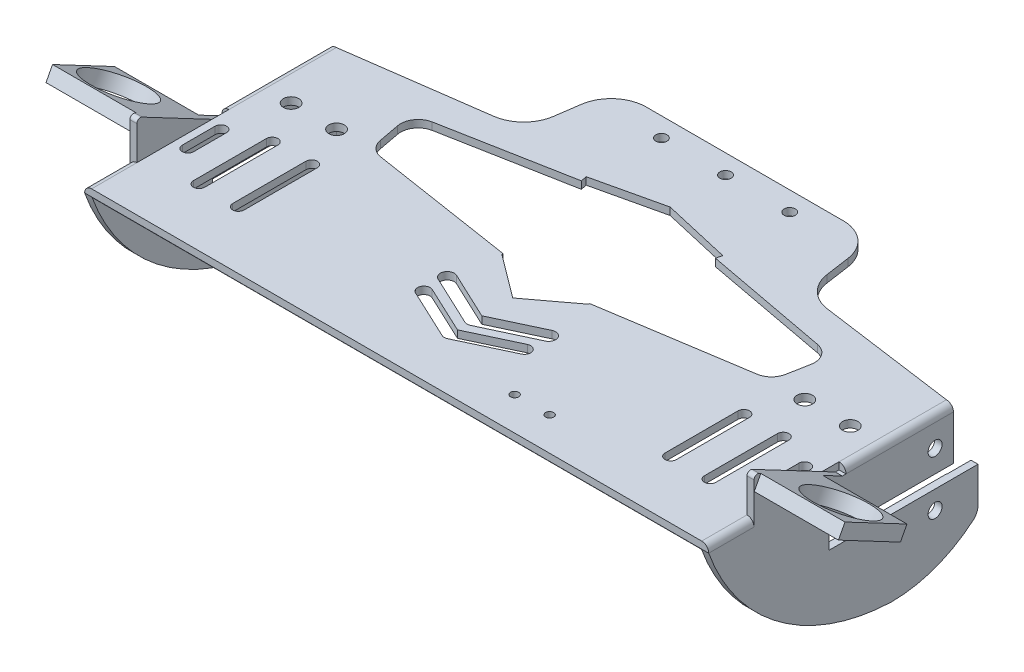
SolidWorks part; units mm, degrees
ref_plane "前视基准面" through (0, 0, 0) normal (0, 0, 1) x (1, 0, 0)
ref_plane "上视基准面" through (0, 0, 0) normal (0, 1, 0) x (1, 0, 0)
ref_plane "右视基准面" through (0, 0, 0) normal (1, 0, 0) x (0, 0, -1)
sketch "草图1" plane through (0, 0, 0) normal (0, 1, 0) x (1, 0, 0)
  line L1 (-89, 49.65) -> (89, 49.65)
  line L2 (-89, 49.65) -> (-89, -49.65)
  line L3 (-89, -49.65) -> (89, -49.65)
  line L4 (89, 49.65) -> (89, -49.65)
  line L5 (-89, 49.65) -> (89, -49.65) construction
  line L6 (-89, -49.65) -> (89, 49.65) construction
  point P0 (0, 0)
  dimension "D1" = 99.3
  dimension "D2" = 178
extrude "凸台-拉伸1" add sketch "草图1" along normal blind 40.1
sketch "草图2" plane through (0, 0, 49.65) normal (0, 0, 1) x (1, 0, 0)
  line L0 (-89, 0) -> (89, 0) construction
  line L1 (-86.9, 0) -> (86.9, 0)
  line L2 (-86.9, 0) -> (-86.9, 38)
  line L3 (-86.9, 38) -> (86.9, 38)
  line L4 (86.9, 0) -> (86.9, 38)
  line L5 (-89, 40.1) -> (89, 40.1) construction
  line L6 (-89, 40.1) -> (-89, 0) construction
  line L7 (89, 40.1) -> (89, 0) construction
  dimension "D1" = 2.1
  dimension "D2" = 2.1
  dimension "D3" = 2.1
extrude "切除-拉伸1" cut sketch "草图2" against normal through all
fillet "圆角2" radius 2 2 edges at (-89, 40.1, 0) (89, 40.1, 0)
sketch "草图4" plane through (0, 40.1, 0) normal (0, 1, 0) x (1, 0, 0)
  line L1 (-87, 49.65) -> (-87, -49.65) construction
  line L4 (87, -49.65) -> (87, 49.65) construction
  line L6 (87, 49.65) -> (-87, 49.65) construction
  line L11 (-36.8, 49.65) -> (-39.0309, 34.1016)
  line L12 (-47.5567, 25.6166) -> (-87, 20.15)
  line L13 (36.8, 49.65) -> (39.0309, 34.1016)
  line L14 (47.5567, 25.6166) -> (87, 20.15)
  line L15 (-36.8, 49.65) -> (-87, 49.65)
  line L16 (36.8, 49.65) -> (87, 49.65)
  line L18 (-87, 49.65) -> (-89, 49.65)
  line L19 (-89, 49.65) -> (-89, 35.5219)
  line L20 (-89, -49.65) -> (-89, 49.65) construction
  line L21 (-89, 35.5219) -> (-87, 35.5219)
  line L22 (-87, 35.5219) -> (-87, 20.15)
  line L23 (87, 49.65) -> (89, 49.65)
  line L24 (89, 49.65) -> (89, 35.5219)
  line L25 (89, 49.65) -> (89, -49.65) construction
  line L26 (89, 35.5219) -> (87, 35.5219)
  line L27 (87, 35.5219) -> (87, 20.15)
  arc A0 (47.5567, 25.6166) -> (39.0309, 34.1016) centre (48.9295, 35.5219) cw
  arc A1 (-47.5567, 25.6166) -> (-39.0309, 34.1016) centre (-48.9295, 35.5219) ccw
  point P6 (40.1, 26.65)
  point P22 (-40.1, 26.65)
  dimension "D1" = 10
  dimension "D3" = 73.6
  dimension "D4" = 80.2
extrude "切除-拉伸2" cut sketch "草图4" against normal through all
sketch "草图6" plane through (0, 40.1, 0) normal (0, 1, 0) x (1, 0, 0)
  line L0 (-36.8, 49.65) -> (-38.031, 41.0702)
  line L1 (-36.8, 49.65) -> (-28.1324, 49.65)
  line L2 (28.1324, 49.65) -> (36.8, 49.65)
  line L3 (36.8, 49.65) -> (38.031, 41.0702)
  arc A0 (38.031, 41.0702) -> (28.1324, 49.65) centre (28.1324, 39.65) ccw
  arc A1 (-28.1324, 49.65) -> (-38.031, 41.0702) centre (-28.1324, 39.65) ccw
  arc A6 (37.501, 43.1471) -> (38.031, 41.0702) centre (67.3147, 49.65) ccw
  dimension "D2" = 10
extrude "切除-拉伸3" cut sketch "草图6" against normal through all contours A0 L0 L1 | A1 L1 L2 region at (-35.1715, 40.1, -47.7712) region at (35.1715, 40.1, -47.7712)
sketch "草图8" plane through (0, 40.1, 0) normal (0, 1, 0) x (1, 0, 0)
  line L0 (0, 0) -> (0, 49.65) construction
  line L1 (28.1324, 49.65) -> (-28.1324, 49.65) construction
  line L2 (0, 28.35) -> (-19.5, 23.8654)
  line L3 (-19.5, 23.8654) -> (-12.3279, -7.3205)
  line L4 (-12.3279, -7.3205) -> (0, -16.55)
  line L5 (0, 0) -> (0, -49.65) construction
  line L6 (-87, -49.65) -> (87, -49.65) construction
  line L7 (12.3279, -7.3205) -> (0, -16.55)
  line L8 (19.5, 23.8654) -> (12.3279, -7.3205)
  line L9 (0, 28.35) -> (19.5, 23.8654)
  line L10 (0, -27.5506) -> (-14.4638, -20.751) construction
  line L11 (-0.8416, -29.3407) -> (-15.3054, -22.5412)
  line L12 (0, -25.3648) -> (-13.6222, -18.9609)
  line L13 (0, -34.2872) -> (-14.33, -27.5506) construction
  line L14 (-0.7615, -35.907) -> (-15.0915, -29.1704)
  line L15 (0, -32.3093) -> (-13.5685, -25.9307)
  line L16 (0, -27.5506) -> (14.4638, -20.751) construction
  line L17 (0.7598, -29.3407) -> (15.3054, -22.5412)
  line L18 (0, -25.3648) -> (13.6222, -18.9609)
  line L19 (0, -34.2872) -> (14.33, -27.5506) construction
  line L20 (0.7615, -35.907) -> (15.0915, -29.1704)
  line L21 (0, -32.3093) -> (13.5685, -25.9307)
  line L22 (22.519, 16.4386) -> (19.6042, 0.9065)
  line L23 (25.2872, -4.9563) -> (53.6458, -0.5436)
  line L24 (57.7913, 3.4748) -> (58.9414, 9.6035)
  line L25 (54.9494, 15.4399) -> (28.3555, 20.4306)
  line L26 (-57.7913, 3.4748) -> (-58.9414, 9.6035)
  line L27 (-25.2872, -4.9563) -> (-53.6458, -0.5436)
  line L28 (-22.519, 16.4386) -> (-19.6042, 0.9065)
  line L29 (-54.9494, 15.4399) -> (-28.3555, 20.4306)
  line L30 (-72.8787, -12.2804) -> (-72.8787, -33.1326) construction
  line L31 (-71.2555, -12.2804) -> (-71.2555, -33.1326)
  line L32 (-74.5019, -12.2804) -> (-74.5019, -33.1326)
  line L33 (-61.641, -12.2804) -> (-61.641, -33.1326) construction
  line L34 (-60.0178, -12.2804) -> (-60.0178, -33.1326)
  line L35 (-63.2642, -12.2804) -> (-63.2642, -33.1326)
  line L36 (-83.2424, -16.55) -> (-83.2424, -25.9307) construction
  line L37 (-81.6191, -16.55) -> (-81.6191, -25.9307)
  line L38 (-84.8656, -16.55) -> (-84.8656, -25.9307)
  line L39 (61.641, -12.2804) -> (61.641, -33.1326) construction
  line L40 (60.0178, -12.2804) -> (60.0178, -33.1326)
  line L41 (63.2642, -12.2804) -> (63.2642, -33.1326)
  line L42 (72.8787, -12.2804) -> (72.8787, -33.1326) construction
  line L43 (71.2555, -12.2804) -> (71.2555, -33.1326)
  line L44 (74.5019, -12.2804) -> (74.5019, -33.1326)
  line L45 (83.2424, -16.55) -> (83.2424, -25.9307) construction
  line L46 (81.6191, -16.55) -> (81.6191, -25.9307)
  line L47 (84.8656, -16.55) -> (84.8656, -25.9307)
  line L48 (-18.3, 49.65) -> (-18.3, 44.15) construction
  line L49 (-27.1278, 49.65) -> (-12.028, 49.65) construction
  line L50 (-18.3, 44.15) -> (0, 44.15) construction
  arc A4 (-13.6222, -18.9609) -> (-15.3054, -22.5412) centre (-14.4638, -20.751) ccw
  arc A6 (-13.5685, -25.9307) -> (-15.0915, -29.1704) centre (-14.33, -27.5506) ccw
  arc A8 (13.6222, -18.9609) -> (15.3054, -22.5412) centre (14.4638, -20.751) cw
  arc A10 (13.5685, -25.9307) -> (15.0915, -29.1704) centre (14.33, -27.5506) cw
  arc A11 (-0.7615, -35.907) -> (0.7615, -35.907) centre (0, -34.2872) ccw
  arc A12 (-0.8416, -29.3407) -> (0.7598, -29.3407) centre (-0.0409, -27.7399) ccw
  arc A13 (58.9414, 9.6035) -> (54.9494, 15.4399) centre (54.0272, 10.5257) ccw
  arc A14 (22.519, 16.4386) -> (28.3555, 20.4306) centre (27.4332, 15.5164) cw
  arc A15 (53.6458, -0.5436) -> (57.7913, 3.4748) centre (52.8771, 4.397) ccw
  arc A16 (19.6042, 0.9065) -> (25.2872, -4.9563) centre (24.5185, -0.0157) ccw
  arc A17 (-58.9414, 9.6035) -> (-54.9494, 15.4399) centre (-54.0272, 10.5257) cw
  arc A18 (-53.6458, -0.5436) -> (-57.7913, 3.4748) centre (-52.8771, 4.397) cw
  arc A19 (-19.6042, 0.9065) -> (-25.2872, -4.9563) centre (-24.5185, -0.0157) cw
  arc A20 (-22.519, 16.4386) -> (-28.3555, 20.4306) centre (-27.4332, 15.5164) ccw
  circle A23 centre (-66.7728, -0.0157) radius 2.2
  circle A24 centre (-79.7448, -0.0157) radius 2.2
  circle A25 centre (79.7448, -0.0157) radius 2.2
  circle A26 centre (66.7728, -0.0157) radius 2.2
  arc A27 (-71.2555, -12.2804) -> (-74.5019, -12.2804) centre (-72.8787, -12.2804) ccw
  arc A28 (-74.5019, -33.1326) -> (-71.2555, -33.1326) centre (-72.8787, -33.1326) ccw
  arc A29 (-60.0178, -12.2804) -> (-63.2642, -12.2804) centre (-61.641, -12.2804) ccw
  arc A30 (-63.2642, -33.1326) -> (-60.0178, -33.1326) centre (-61.641, -33.1326) ccw
  arc A31 (-81.6191, -16.55) -> (-84.8656, -16.55) centre (-83.2424, -16.55) ccw
  arc A32 (-84.8656, -25.9307) -> (-81.6191, -25.9307) centre (-83.2424, -25.9307) ccw
  arc A33 (60.0178, -12.2804) -> (63.2642, -12.2804) centre (61.641, -12.2804) cw
  arc A34 (63.2642, -33.1326) -> (60.0178, -33.1326) centre (61.641, -33.1326) cw
  arc A35 (71.2555, -12.2804) -> (74.5019, -12.2804) centre (72.8787, -12.2804) cw
  arc A36 (74.5019, -33.1326) -> (71.2555, -33.1326) centre (72.8787, -33.1326) cw
  arc A37 (81.6191, -16.55) -> (84.8656, -16.55) centre (83.2424, -16.55) cw
  arc A38 (84.8656, -25.9307) -> (81.6191, -25.9307) centre (83.2424, -25.9307) cw
  circle A42 centre (-18.3, 44.15) radius 1.6
  circle A43 centre (0, 44.15) radius 1.6
  circle A44 centre (18.3, 44.15) radius 1.6
  point P7 (0, 40.65)
  point P24 (-7.2319, -24.1508)
  point P29 (-7.165, -30.9189)
  point P42 (7.2319, -24.1508)
  point P49 (7.165, -30.9189)
  point P72 (-72.8787, -22.7065)
  point P89 (-61.641, -22.7065)
  point P96 (-83.2424, -21.2403)
  point P103 (61.641, -22.7065)
  point P110 (72.8787, -22.7065)
  point P117 (83.2424, -21.2403)
  dimension "D11" = 1.9781
  dimension "D12" = 1.7899
  dimension "D13" = 1.7899
  dimension "D14" = 5
  dimension "D15" = 5
  dimension "D16" = 4.4
  dimension "D17" = 4.4
  dimension "D7" = 44.9
  dimension "D8" = 39
  dimension "D9" = 32
  dimension "D10" = 15.4
extrude "切除-拉伸4" cut sketch "草图8" against normal through all
sketch "草图9" plane through (-89, 0, 0) normal (-1, 0, 0) x (0, 0, 1)
  line L4 (-3.9924, 34.7018) -> (22.4339, 34.7018)
  line L5 (22.3848, 35.6994) -> (37.5202, 37.1925)
  line L6 (37.5693, 37.1949) -> (-3.4557, 37.1949)
  line L7 (-3.9262, 36.8641) -> (-4.4629, 35.3709)
  arc A4 (37.5202, 37.1925) -> (37.5693, 37.1949) centre (37.5693, 36.6949) ccw
  arc A5 (-3.4557, 37.1949) -> (-3.9262, 36.8641) centre (-3.4557, 36.6949) ccw
  arc A6 (22.4339, 34.7018) -> (22.3848, 35.6994) centre (22.4339, 35.2018) ccw
  arc A7 (-3.9924, 34.7018) -> (-4.4629, 35.3709) centre (-3.9924, 35.2018) cw
  dimension "D1" = 0.5
sketch "草图11" plane through (-89, 0, 0) normal (-1, 0, 0) x (0, 0, 1)
  line L0 (-35.5219, 0) -> (49.65, 0) construction
  line L1 (-20.15, 0) -> (-20.15, 40.1) construction
  line L2 (-20.15, 31.5533) -> (-20.15, 40.1)
  line L3 (-35.5219, 0) -> (-35.5219, 38.1) construction
  line L4 (-20.15, 31.5533) -> (-35.5219, 31.5533)
  line L5 (-35.5219, 31.5533) -> (-35.5219, 25.3757)
  line L6 (-35.5219, 25.3757) -> (15.2781, 25.3757)
  line L7 (15.2781, 25.3757) -> (15.2781, 21.6757)
  line L8 (15.2781, 21.6757) -> (-35.5219, 21.6757)
  line L9 (49.65, 38.1) -> (49.65, 0) construction
  line L10 (-20.15, 40.1) -> (-35.5219, 40.1)
  line L11 (-35.5219, 40.1) -> (-35.5219, 31.5533)
  line L12 (-35.5219, 25.3757) -> (-35.5219, 21.6757)
  line L13 (-35.5219, 21.6757) -> (-35.5219, 0)
  line L14 (-35.5219, 0) -> (-8.2396, 0)
  line L15 (-6.3135, 0) -> (49.65, 0)
  line L16 (49.65, 0) -> (49.65, 38.1)
  arc A0 (49.65, 38.1) -> (-6.3135, 0) centre (-4.4168, 57.3652) cw
  arc A1 (-35.5219, 21.6757) -> (-8.2396, 0) centre (1.0945, 39.7558) ccw
  line M11 (49.65, 38.1) -> (-35.5219, 38.1)
  line M12 (-35.5219, 38.1) -> (-35.5219, 0)
  line M13 (-35.5219, 0) -> (49.65, 0)
  line M14 (49.65, 0) -> (49.65, 38.1)
  dimension "D1" = 50.8
  dimension "D2" = 34.3719
  dimension "D3" = 3.7
extrude "切除-拉伸6" cut sketch "草图11" against normal up to next contours L4 L2 M11 M12 | L10 L11 L2 M11 | A1 M12 M13 | A0 L15 M14 | L8 L7 L6 M12 region at (-89, 34.8267, -27.8359) region at (-89, 39.1, -27.8359) region at (-89, 10.263, 37.2191) region at (-89, 23.5257, -10.1219) region at (-89, 6.1552, -28.0302)
sketch "草图12" plane through (89, 0, 0) normal (1, 0, 0) x (0, 0, -1)
  line L9 (35.5219, 40.1) -> (35.5219, 31.5533) construction
  line L10 (20.15, 40.1) -> (35.5219, 40.1) construction
  line L11 (20.15, 31.5533) -> (20.15, 40.1) construction
  line L12 (20.15, 31.5533) -> (35.5219, 31.5533) construction
  line L14 (35.5219, 25.3757) -> (-15.3185, 25.3757)
  line L15 (-15.3185, 25.3757) -> (-15.3185, 21.6757)
  line L16 (-15.3185, 21.6757) -> (35.5219, 21.6757)
  line L17 (35.5219, 25.3757) -> (35.5219, 21.6757)
  line L22 (35.5219, 40.1) -> (35.5219, 31.5533)
  line L23 (20.15, 40.1) -> (35.5219, 40.1)
  line L24 (20.15, 31.5533) -> (20.15, 40.1)
  line L25 (20.15, 31.5533) -> (35.5219, 31.5533)
  dimension "D1" = 50.8404
extrude "切除-拉伸7" cut sketch "草图12" against normal up to next
sketch "草图13" plane through (89, 0, 0) normal (1, 0, 0) x (0, 0, -1)
  line L3 (2.5201, 0) -> (35.5219, 0) construction
  line L4 (35.5219, 21.6757) -> (35.5219, 0)
  line L5 (35.5219, 0) -> (2.5201, 0)
  arc A1 (2.5201, 0) -> (35.5219, 21.6757) centre (2.5201, 35.9609) ccw
  arc A2 (-49.65, 38.1) -> (2.5201, 0) centre (4.4168, 57.3652) ccw construction
extrude "切除-拉伸8" cut sketch "草图13" against normal through all
sketch "草图14" plane through (-89, 0, 0) normal (-1, 0, 0) x (0, 0, 1)
  line L1 (-20.15, 31.5533) -> (-35.5219, 31.5533)
  line L2 (-20.15, 31.5533) -> (-20.15, 25.3757)
  line L3 (-20.15, 25.3757) -> (-35.5219, 25.3757)
  line L4 (-35.5219, 31.5533) -> (-35.5219, 25.3757)
extrude "切除-拉伸9" cut sketch "草图14" against normal through all both and the other way through all
fillet "圆角5" radius 2 1 edges at (-88, 21.6757, -35.5219) type face fillet first side face at (-87.6333, 21.6757, -13.4669) second side face at (-87.6333, 9.124, -24.1133)
fillet "圆角6" radius 2 1 edges at (88, 21.6757, -35.5219) type face fillet first side face at (87.6333, 21.6757, -13.4534) second side face at (87.6333, 7.544, -20.2225)
sketch "草图15" plane through (89, 0, 0) normal (1, 0, 0) x (0, 0, -1)
  line L0 (-49.65, 38.1) -> (-15.0631, 38.1) construction
  line L1 (20.15, 38.1) -> (-49.65, 38.1) construction
  line L2 (7.3369, 38.1) -> (-37.4631, 38.1)
  line L3 (-37.4631, 38.1) -> (-37.4631, 27.6)
  line L4 (-37.4631, 27.6) -> (7.3369, 27.6)
  line L5 (7.3369, 27.6) -> (7.3369, 38.1)
  point P8 (-15.0631, 38.1)
extrude "凸台-拉伸2" add sketch "草图15" along normal blind 2
sketch "草图16" plane through (91, 0, 0) normal (1, 0, 0) x (0, 0, -1)
  line L0 (-37.4631, 38.1) -> (-21.8983, 38.1) construction
  line L1 (7.3369, 38.1) -> (-37.4631, 38.1) construction
  line L2 (-21.8983, 32.7435) -> (-21.8983, 54.1985) construction
  line L3 (-30.0183, 43.93) -> (-21.8983, 38.1) construction
  line L4 (-30.0183, 38.1) -> (-30.0183, 43.93) construction
  line L5 (-21.8983, 38.1) -> (-13.7752, 32.2678) construction
  line L6 (-30.6015, 43.1177) -> (-29.4351, 44.7423)
  line L7 (-30.6015, 43.1177) -> (-31.7823, 41.4732)
  line L8 (-31.7823, 41.4732) -> (-15.536, 29.8087)
  line L9 (-15.536, 29.8087) -> (-13.2032, 33.0579)
  line L10 (-29.4351, 44.7423) -> (-13.2032, 33.0579)
  point P10 (-21.8983, 38.1)
  point P14 (-30.0183, 43.93)
  dimension "D1" = 8.12
extrude "凸台-拉伸3" add sketch "草图16" along normal blind 20
sketch "草图17" plane through (0, 15.5146, -11.168) normal (0, 0.8116, -0.5842) x (1, 0, 0)
  line L0 (91, -50.0287) -> (111, -30.0287) construction
  line L1 (91, -30.0287) -> (111, -50.0287) construction
  circle A0 centre (101, -40.0287) radius 9
extrude "切除-拉伸10" cut sketch "草图17" against normal blind 5
sketch "草图18" plane through (89, 0, 0) normal (1, 0, 0) x (0, 0, -1)
  line L0 (-32.4893, 38.1) -> (-32.4893, 54.845) construction
  line L4 (-20.071, 38.1) -> (-20.071, 54.845)
  line L5 (-32.4893, 54.845) -> (-20.071, 54.845)
  line L6 (-32.4893, 38.1) -> (-20.071, 38.1)
  line L7 (-32.4893, 54.845) -> (-32.4893, 38.1)
extrude "切除-拉伸11" cut sketch "草图18" against normal blind 2
sketch "草图19" plane through (91, 0, 0) normal (-1, 0, 0) x (0, 0, 1)
  line L0 (20.2076, 38.1) -> (29.4351, 44.7423)
  line L1 (31.7823, 33.3445) -> (31.7823, 49.6018) construction
  line L3 (29.4351, 44.7423) -> (31.7823, 46.4319)
  line L4 (31.7823, 46.4319) -> (31.7823, 41.4732)
  line L5 (20.2076, 38.1) -> (34.2826, 38.1) construction
  line L6 (27.0842, 38.1) -> (37.4631, 38.1) construction
  line L7 (20.2076, 38.1) -> (31.7823, 38.1)
  line L8 (31.7823, 38.1) -> (31.7823, 41.4732)
  point P9 (31.7823, 41.4732)
extrude "凸台-拉伸4" add sketch "草图19" along normal blind 4
sketch "草图20" plane through (87, 0, 0) normal (-1, 0, 0) x (0, 0, 1)
  line L0 (22.986, 40.1) -> (31.7823, 40.1)
  line L1 (31.7823, 40.1) -> (31.7823, 46.4319)
  line L2 (31.7823, 46.4319) -> (22.986, 40.1)
extrude "凸台-拉伸5" add sketch "草图20" along normal blind 1.5
ref_plane "基准面1" through (0, 0, 0) normal (-1, 0, 0) x (0, 1, 0)
sketch "草图21" plane through (-89, 0, 0) normal (-1, 0, 0) x (0, 0, 1)
  line L0 (49.65, 38.1) -> (-20.15, 38.1) construction
  line L1 (19.0608, 38.1) -> (32.4979, 38.1)
  line L2 (19.0608, 38.1) -> (19.0608, 58.3811)
  line L3 (19.0608, 58.3811) -> (32.4979, 58.3811)
  line L4 (32.4979, 38.1) -> (32.4979, 58.3811)
extrude "切除-拉伸12" cut sketch "草图21" against normal blind 2
mirror "镜向2" about plane through (0, 0, 0) normal (-1, 0, 0) of "凸台-拉伸5", "凸台-拉伸2", "凸台-拉伸3", "切除-拉伸10", "凸台-拉伸4"
sketch "草图22" plane through (0, 40.1, 0) normal (0, 1, 0) x (1, 0, 0)
  line L0 (-38.9134, 18.4493) -> (-28.3555, 20.4306) construction
  line L2 (-28.3555, 20.4306) -> (-54.9494, 15.4399) construction
  line L3 (-28.3555, 20.4306) -> (0, 25.7518) construction
  line L4 (0, 110.453) -> (0, -110.453) construction
  line L5 (-28.3555, 20.4306) -> (-19.1091, 22.1658)
  line L6 (-19.5, 23.8654) -> (-12.3279, -7.3205) construction
  line L7 (-33.1335, -3.7354) -> (-25.2872, -4.9563) construction
  line L8 (-53.6458, -0.5436) -> (-25.2872, -4.9563) construction
  line L9 (-25.2872, -4.9563) -> (0, -8.891) construction
  line L10 (-19.1091, 22.1658) -> (-12.4108, -6.9599)
  line L11 (-12.4108, -6.9599) -> (-25.2872, -4.9563)
  line L12 (-22.519, 16.4386) -> (-19.6042, 0.9065)
  line L13 (28.3555, 20.4306) -> (19.1091, 22.1658)
  line L14 (19.1091, 22.1658) -> (12.4108, -6.9599)
  line L15 (12.4108, -6.9599) -> (25.2872, -4.9563)
  line L16 (22.519, 16.4386) -> (19.6042, 0.9065)
  arc A0 (-25.2872, -4.9563) -> (-19.6042, 0.9065) centre (-24.5185, -0.0157) ccw
  arc A1 (-28.3555, 20.4306) -> (-22.519, 16.4386) centre (-27.4332, 15.5164) cw
  arc A2 (28.3555, 20.4306) -> (22.519, 16.4386) centre (27.4332, 15.5164) ccw
  arc A3 (25.2872, -4.9563) -> (19.6042, 0.9065) centre (24.5185, -0.0157) cw
extrude "切除-拉伸13" cut sketch "草图22" against normal blind 6
ref_plane "基准面2" through (0, 30.6223, 42.6506) normal (0, 0.5832, 0.8123) x (1, 0, 0)
sketch "草图23" plane through (0, 30.6223, 42.6506) normal (0, 0.5832, 0.8123) x (1, 0, 0)
  line L1 (-96.792, 24.8771) -> (-78.9143, 24.8771)
  line L2 (-96.792, 24.8771) -> (-96.792, 16.5031)
  line L3 (-96.792, 16.5031) -> (-78.9143, 16.5031)
  line L4 (-78.9143, 24.8771) -> (-78.9143, 16.5031)
  line L5 (81.9311, 26.5695) -> (95.5678, 26.5695)
  line L6 (81.9311, 26.5695) -> (81.9311, 13.5683)
  line L7 (81.9311, 13.5683) -> (95.5678, 13.5683)
  line L8 (95.5678, 26.5695) -> (95.5678, 13.5683)
extrude "切除-拉伸14" cut sketch "草图23" along normal blind 4
fillet "圆角12" radius 0.5 2 edges at (-88.25, 46.2029, 31.4641) (-88.25, 45.7597, 31.7823)
sketch "草图25" plane through (0, 40.1, 0) normal (0, 1, 0) x (1, 0, 0)
  line L0 (29.1327, -49.65) -> (29.1327, -40.15) construction
  line L1 (-87, -49.65) -> (87, -49.65) construction
  line L2 (34.1327, -40.15) -> (24.1327, -40.15) construction
  circle A0 centre (24.1327, -40.15) radius 1.15
  circle A1 centre (34.1327, -40.15) radius 1.15
  point P7 (29.1327, -40.15)
extrude "切除-拉伸15" cut sketch "草图25" against normal blind 5
sketch "草图28" plane through (91, 0, 0) normal (1, 0, 0) x (0, 0, -1)
  line L0 (-31.7823, 38.1) -> (-37.4631, 38.1)
  line L1 (-37.4631, 38.1) -> (-37.4631, 27.6)
  line L2 (-37.4631, 27.6) -> (7.3369, 27.6)
  line L3 (7.3369, 27.6) -> (7.3369, 38.1)
  line L4 (7.3369, 38.1) -> (-12.0153, 38.1)
  line L5 (7.3369, 38.1) -> (-20.2076, 38.1) construction
  line L8 (-31.7823, 29.3719) -> (-31.7823, 38.1)
  line L9 (-13.2032, 33.0579) -> (-13.2032, 38.1)
  line L10 (-13.2032, 38.1) -> (-12.0153, 38.1)
  line L11 (-13.2032, 33.0579) -> (-13.2032, 29.3719)
  line L12 (-13.2032, 29.3719) -> (-31.7823, 29.3719)
extrude "切除-拉伸17" cut sketch "草图28" against normal blind 2
mirror "镜向3" about plane through (0, 0, 0) normal (-1, 0, 0) of "切除-拉伸17"
sketch "草图30" plane through (-91, 0, 0) normal (-1, 0, 0) x (0, 0, 1)
  line L0 (15.536, 29.8087) -> (31.7823, 41.4732)
  line L1 (31.7823, 41.4732) -> (31.7823, 29.3719)
  line L2 (31.7823, 29.3719) -> (14.9277, 29.3719)
  line L3 (13.2032, 29.3719) -> (31.7823, 29.3719) construction
  line L4 (14.9277, 29.3719) -> (15.536, 29.8087)
  line L5 (13.2032, 33.0579) -> (13.2032, 38.1)
  line L6 (13.2032, 38.1) -> (20.2076, 38.1)
  line L7 (20.2076, 38.1) -> (13.2032, 33.0579)
extrude "切除-拉伸18" cut sketch "草图30" against normal blind 2
mirror "镜向4" about plane through (0, 0, 0) normal (-1, 0, 0) of "切除-拉伸18"
ref_plane "基准面3" through (0, 0, -28.35) normal (0, 0, 1) x (0, 1, 0)
sketch "草图31" plane through (0, 0, -28.35) normal (0, 0, 1) x (0, 1, 0)
  line L1 (-427.3418, 522.2605) -> (309.4249, 522.2605)
  line L2 (-427.3418, 522.2605) -> (-427.3418, -182.3113)
  line L3 (-427.3418, -182.3113) -> (309.4249, -182.3113)
  line L4 (309.4249, 522.2605) -> (309.4249, -182.3113)
  line L5 (-58.9585, -182.3113) -> (-58.9585, 522.2605) construction
  line L6 (-427.3418, 169.9746) -> (309.4249, 169.9746) construction
  point P0 (-58.9585, 169.9746)
sketch "草图32" plane through (0, 38, 0) normal (0, -1, 0) x (1, 0, 0)
  line L1 (-436.9216, 77.7709) -> (139.7289, 77.7709)
  line L2 (-436.9216, 77.7709) -> (-436.9216, -72.8793)
  line L3 (-436.9216, -72.8793) -> (139.7289, -72.8793)
  line L4 (139.7289, 77.7709) -> (139.7289, -72.8793)
  line L5 (-148.5964, -72.8793) -> (-148.5964, 77.7709) construction
  line L6 (-436.9216, 2.4458) -> (139.7289, 2.4458) construction
  point P0 (-148.5964, 2.4458)
sketch "草图33" plane through (89, 0, 0) normal (1, 0, 0) x (0, 0, -1)
  line L1 (-185.5229, 149.1045) -> (54.0964, 149.1045)
  line L2 (-185.5229, 149.1045) -> (-185.5229, -12.2806)
  line L3 (-185.5229, -12.2806) -> (54.0964, -12.2806)
  line L4 (54.0964, 149.1045) -> (54.0964, -12.2806)
  line L5 (-65.7132, -12.2806) -> (-65.7132, 149.1045) construction
  line L6 (-185.5229, 68.4119) -> (54.0964, 68.4119) construction
  point P0 (-65.7132, 68.4119)
extrude "切除-拉伸19" cut sketch "草图33" along normal blind 35
mirror "镜向5" about plane through (0, 0, 0) normal (-1, 0, 0) of "切除-拉伸19"
sketch "草图35" plane through (0, 40.1, 0) normal (0, 1, 0) x (1, 0, 0)
  line L1 (-354.4157, 220.6911) -> (125.4327, 220.6911)
  line L2 (-354.4157, 220.6911) -> (-354.4157, -72.8161)
  line L3 (-354.4157, -72.8161) -> (125.4327, -72.8161)
  line L4 (125.4327, 220.6911) -> (125.4327, -72.8161)
  line L5 (-114.4915, -72.8161) -> (-114.4915, 220.6911) construction
  line L6 (-354.4157, 73.9375) -> (125.4327, 73.9375) construction
  point P0 (-114.4915, 73.9375)
extrude "切除-拉伸20" cut sketch "草图35" along normal blind 13
sketch "草图36" plane through (87, 0, 0) normal (1, 0, 0) x (0, 0, -1)
  line L0 (-20.2076, 38.1) -> (22.4629, 38.1) construction
  line L6 (22.4629, 38.1) -> (-53.4174, 38.1)
  line L7 (22.4629, 38.1) -> (22.4629, 43.7746)
  line L8 (22.4629, 43.7746) -> (-53.4174, 43.7746)
  line L9 (-53.4174, 38.1) -> (-53.4174, 43.7746)
extrude "切除-拉伸21" cut sketch "草图36" along normal blind 2
mirror "镜向6" about plane through (0, 0, 0) normal (-1, 0, 0) of "切除-拉伸21"
sketch "草图38" plane through (89, 0, 0) normal (1, 0, 0) x (0, 0, -1)
  line L0 (14.9041, -3.9584) -> (14.9041, 47.3099) construction
  line L2 (20.15, 31.7379) -> (9.2217, 31.7379) construction
  line L3 (20.15, 38.1) -> (20.15, 25.3757) construction
  circle A0 centre (14.9041, 31.7379) radius 2
  circle A1 centre (14.9041, 16.3888) radius 2
  point P3 (14.9041, 21.6757)
sketch "草图39" plane through (87, 0, 0) normal (1, 0, 0) x (0, 0, -1)
  line L1 (-49.65, 38.1) -> (20.15, 38.1)
  line L2 (-49.65, 38.1) -> (-49.65, 40.1)
  line L3 (-49.65, 40.1) -> (20.15, 40.1)
  line L4 (20.15, 38.1) -> (20.15, 40.1)
extrude "凸台-拉伸6" add sketch "草图39" along normal blind 2
extrude "切除-拉伸25" cut sketch "草图38" against normal blind 201
mirror "镜向7" about plane through (0, 0, 0) normal (-1, 0, 0) of "凸台-拉伸6"
fillet "圆角13" radius 2 2 edges at (89, 40.1, 14.75) (-89, 40.1, 14.75)
sketch "草图40" plane through (89, 0, 0) normal (1, 0, 0) x (0, 0, -1)
  line L14 (20.15, 38.1) -> (-49.65, 38.1) construction
  line L16 (-26.65, 40.3587) -> (-22.3612, 40.3587)
  line L18 (-22.3612, 38.1) -> (-26.65, 38.1)
  line L24 (-21.0026, 40.3587) -> (-22.3612, 40.3587)
  line L25 (-21.0026, 38.1) -> (-22.3612, 38.1)
  line L29 (-36.7356, 40.3587) -> (-36.7356, 38.1)
  line L30 (-36.7356, 40.3587) -> (-26.65, 40.3587)
  line L31 (-26.65, 38.1) -> (-36.7356, 38.1)
  line L32 (-21.0026, 40.3587) -> (-14.147, 40.3587)
  line L34 (-14.147, 38.1) -> (-21.0026, 38.1)
  line L35 (-14.147, 40.3587) -> (-10.4924, 40.3587)
  line L36 (-10.4924, 40.3587) -> (-10.4924, 38.1)
  line L37 (-10.4924, 38.1) -> (-14.147, 38.1)
extrude "切除-拉伸22" cut sketch "草图40" against normal blind 2
mirror "镜向8" about plane through (0, 0, 0) normal (-1, 0, 0) of "切除-拉伸22"
sketch "草图41" plane through (87, 0, 0) normal (1, 0, 0) x (0, 0, -1)
  line L41 (-36.7356, 38.1) -> (-11.5356, 38.1)
  line L42 (-36.7356, 38.1) -> (-10.4924, 38.1) construction
  line L43 (-36.7356, 38.1) -> (-36.7356, 51.4)
  line L44 (-36.7356, 51.4) -> (-11.5356, 38.1)
extrude "凸台-拉伸7" add sketch "草图41" along normal blind 2
ref_plane "基准面4" through (0, 0, -2.4158) normal (0, 0, -1) x (-1, 0, 0)
sketch "草图50" plane through (89, 0, 0) normal (1, 0, 0) x (0, 0, -1)
  line L0 (-36.7356, 51.4) -> (-34.7899, 50.3731) construction
  line L1 (-11.5356, 38.1) -> (-36.7356, 51.4) construction
  line L2 (-34.7899, 50.3731) -> (-36.657, 46.8356)
  line L3 (-36.657, 46.8356) -> (-18.9693, 37.5004)
  line L4 (-18.9693, 37.5004) -> (-17.1023, 41.038)
  line L5 (-17.1023, 41.038) -> (-34.7899, 50.3731)
extrude "凸台-拉伸8" add sketch "草图50" along normal blind 24
sketch "草图51" plane through (0, 25.0376, -13.2143) normal (0, 0.8844, -0.4668) x (1, 0, 0)
  line L0 (89, -34.2798) -> (93, -34.2798) construction
  line L1 (113, -34.2798) -> (89, -34.2798) construction
  line L2 (93, -54.2798) -> (113, -54.2798) construction
  line L3 (113, -54.2798) -> (89, -54.2798) construction
  line L4 (113, -54.2798) -> (93, -34.2798) construction
  circle A0 centre (103, -44.2798) radius 9
extrude "切除-拉伸26" cut sketch "草图51" against normal blind 5
sketch "草图46" plane through (86.9, 0, 0) normal (-1, 0, 0) x (0, 0, 1)
  line L1 (-170.6973, 199.2416) -> (57.4419, 199.2416)
  line L2 (-170.6973, 199.2416) -> (-170.6973, -47.1001)
  line L3 (-170.6973, -47.1001) -> (57.4419, -47.1001)
  line L4 (57.4419, 199.2416) -> (57.4419, -47.1001)
sketch "草图49" plane through (0, 0, -2.4158) normal (0, 0, -1) x (-1, 0, 0)
  line L1 (-107.9659, 70.2705) -> (-46.9748, 70.2705)
  line L2 (-107.9659, 70.2705) -> (-107.9659, -31.3057)
  line L3 (-107.9659, -31.3057) -> (-46.9748, -31.3057)
  line L4 (-46.9748, 70.2705) -> (-46.9748, -31.3057)
mirror "镜向9" about plane through (0, 0, 0) normal (-1, 0, 0) of "凸台-拉伸7"
mirror "镜向10" about plane through (0, 0, 0) normal (-1, 0, 0) of "凸台-拉伸8"
mirror "镜向11" about plane through (0, 0, 0) normal (-1, 0, 0) of "切除-拉伸26"
fillet "圆角14" radius 1 2 edges at (-88, 51.4, 36.7356) (88, 51.4, 36.7356)
sketch "草图52" plane through (89, 0, 0) normal (1, 0, 0) x (0, 0, -1)
  line L0 (20.15, 25.3757) -> (20.15, 0.7762) construction
  line L1 (20.15, 21.6757) -> (34.15, 21.6757) construction
  line L2 (-15.3185, 21.6757) -> (32.3217, 21.6757) construction
  line L4 (27.15, 21.6757) -> (37.5383, 21.6757)
  line L5 (27.15, 21.6757) -> (27.15, 8.1775)
  line L6 (27.15, 8.1775) -> (37.5383, 8.1775)
  line L7 (37.5383, 21.6757) -> (37.5383, 8.1775)
extrude "切除-拉伸27" cut sketch "草图52" against normal blind 178
fillet "圆角16" radius 4 2 edges at (-88, 10.2618, -27.15) (88, 9.7588, -27.15)
